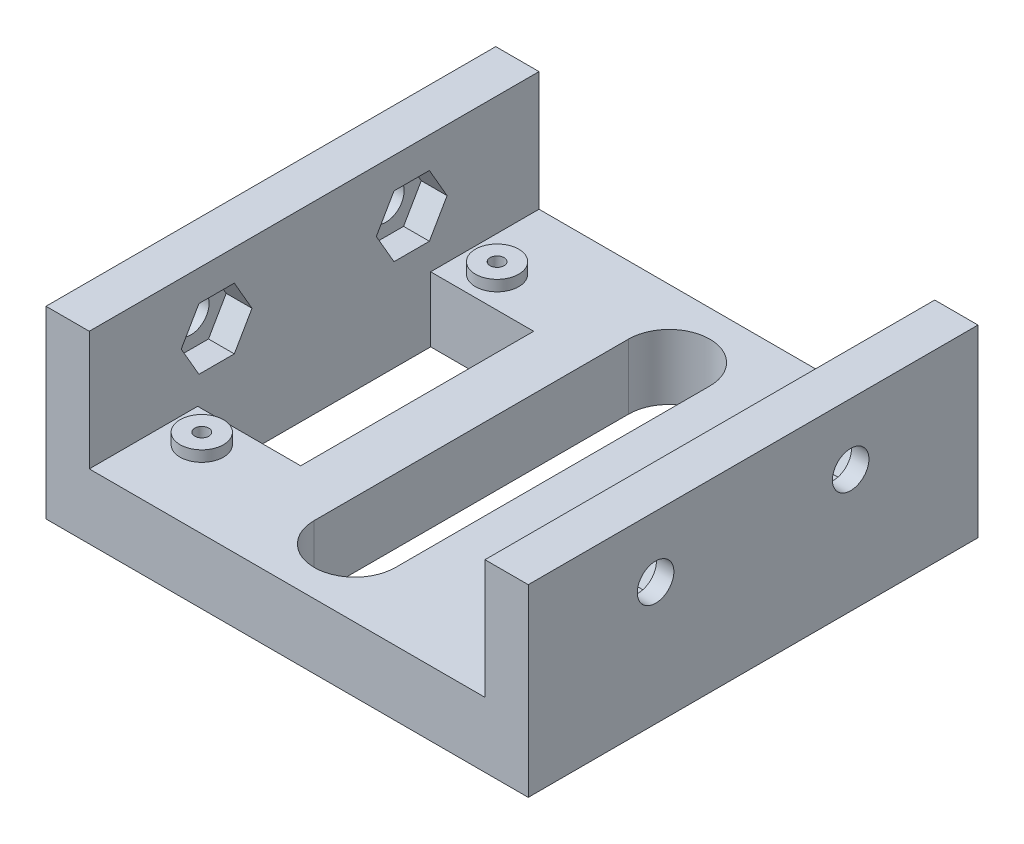
SolidWorks part; units mm, degrees
ref_plane "Front Plane" through (0, 0, 0) normal (0, 0, 1) x (1, 0, 0)
ref_plane "Top Plane" through (0, 0, 0) normal (0, 1, 0) x (1, 0, 0)
ref_plane "Right Plane" through (0, 0, 0) normal (1, 0, 0) x (0, 0, -1)
sketch "Sketch1" plane through (0, 0, 0) normal (0, 1, 0) x (1, 0, 0)
  line L9 (-44.5, 0) -> (44.5, 0)
  line L10 (-44.5, 0) -> (-44.5, 83)
  line L11 (-44.5, 83) -> (44.5, 83)
  line L12 (44.5, 0) -> (44.5, 83)
  line L13 (34.5, 0) -> (-34.5, 0) construction
  line L14 (34.5, 0) -> (34.5, 83) construction
  line L15 (34.5, 83) -> (-34.5, 83) construction
  line L16 (-34.5, 0) -> (-34.5, 83) construction
  line L21 (-30, 14.25) -> (30, 14.25) construction
  line L22 (-30, 14.25) -> (-30, 68.75) construction
  line L23 (-30, 68.75) -> (30, 68.75) construction
  line L24 (30, 14.25) -> (30, 68.75) construction
  line L27 (-7.5, 70.5) -> (-7.5, 12.5)
  line L29 (7.5, 12.5) -> (7.5, 70.5)
  circle A0 centre (30, 14.25) radius 1.3
  circle A1 centre (-30, 14.25) radius 1.3
  circle A2 centre (-30, 68.75) radius 1.3
  circle A3 centre (30, 68.75) radius 1.3
  circle A4 centre (-30, 68.75) radius 1.75 construction
  circle A6 centre (0, 70.5) radius 7.5
  circle A7 centre (0, 12.5) radius 7.5
  point P9 (0, 0)
  point P10 (0, 0)
  point P25 (0, 14.25)
  point P27 (44.5, 41.5)
  point P28 (30, 41.5)
  dimension "D7" = 2.6
  dimension "D8" = 3.5
  dimension "D1" = 83
  dimension "D2" = 69
  dimension "D3" = 10
  dimension "D4" = 15
  dimension "D5" = 5
  dimension "D6" = 5
  dimension "D9" = 60
  dimension "D10" = 54.5
extrude "Main Body" add sketch "Sketch1" along normal blind 14 contours L9 L12 L11 L10 A3 A2 A1 A0 region at (-43.283, 0, -41.5)
sketch "Sketch2" plane through (0, 14, 0) normal (0, 1, 0) x (1, 0, 0)
  line L1 (-36.5125, 0) -> (36.5125, 0)
  line L2 (-36.5125, 0) -> (-36.5125, 83)
  line L3 (-36.5125, 83) -> (36.5125, 83)
  line L4 (36.5125, 0) -> (36.5125, 83)
  line L7 (-44.5, 83) -> (44.5, 83) construction
  circle A2 centre (-30, 14.25) radius 4
  circle A3 centre (30, 14.25) radius 4
  circle A4 centre (-30, 68.75) radius 4
  circle A5 centre (30, 68.75) radius 4
  point P8 (0, 0)
  dimension "D2" = 8
  dimension "D1" = 73.025
extrude "Screw Riser" cut sketch "Sketch2" against normal blind 2
sketch "Sketch4" plane through (0, 14, 0) normal (0, 1, 0) x (1, 0, 0)
  line L0 (-44.5, 0) -> (-36.5125, 0) construction
  line L1 (-44.5, 83) -> (-36.5125, 83)
  line L2 (-44.5, 83) -> (-44.5, 0)
  line L3 (-44.5, 0) -> (-36.5125, 0)
  line L4 (-36.5125, 83) -> (-36.5125, 0)
  line L5 (36.5125, 83) -> (44.5, 83) construction
  line L6 (44.5, 0) -> (36.5125, 0)
  line L7 (44.5, 0) -> (44.5, 83)
  line L8 (44.5, 83) -> (36.5125, 83)
  line L9 (36.5125, 0) -> (36.5125, 83)
extrude "Topper Support" add sketch "Sketch4" along normal offset from surface (20 mm away) 34 up to face at (0, 0, -41.5)
sketch "Sketch6" plane through (-44.5, 0, 0) normal (-1, 0, 0) x (0, 0, 1)
  line L0 (-52.9696, 22.6555) -> (-56.2348, 28.3109)
  line L1 (-53.0842, 22.6555) -> (-56.2921, 28.2117) construction
  line L2 (-56.2921, 28.2117) -> (-62.7079, 28.2117) construction
  line L3 (-62.7079, 28.2117) -> (-65.9158, 22.6555) construction
  line L4 (-65.9158, 22.6555) -> (-62.7079, 17.0992) construction
  line L5 (-62.7079, 17.0992) -> (-56.2921, 17.0992) construction
  line L6 (-56.2921, 17.0992) -> (-53.0842, 22.6555) construction
  line L7 (-56.2348, 28.3109) -> (-62.7652, 28.3109)
  line L8 (-62.7652, 28.3109) -> (-66.0304, 22.6555)
  line L9 (-66.0304, 22.6555) -> (-62.7652, 17)
  line L10 (-62.7652, 17) -> (-56.2348, 17)
  line L11 (-56.2348, 17) -> (-52.9696, 22.6555)
  line L12 (-23.5, 22.6555) -> (-59.5, 22.6555) construction
  line L13 (-16.9696, 22.6555) -> (-20.2348, 28.3109)
  line L14 (-20.2348, 28.3109) -> (-26.7652, 28.3109)
  line L15 (-26.7652, 28.3109) -> (-30.0304, 22.6555)
  line L16 (-30.0304, 22.6555) -> (-26.7652, 17)
  line L17 (-26.7652, 17) -> (-20.2348, 17)
  line L18 (-20.2348, 17) -> (-16.9696, 22.6555)
  line L19 (0, 0) -> (-83, 0) construction
  line L20 (-83, 34) -> (0, 34) construction
  circle A0 centre (-59.5, 22.6555) radius 5.5563 construction
  circle A1 centre (-23.5, 22.6555) radius 5.6555 construction
  point P26 (-41.5, 0)
  point P27 (-41.5, 22.6555)
  dimension "D1" = 11.1125
  dimension "D3" = 36
  dimension "D4" = 17
  dimension "D2" = 0.0992
extrude "Mount Nuts" cut sketch "Sketch6" along normal offset from surface (41.275 mm away) 4.7625 from surface up to face at (-36.5125, 23, -41.5) offset beyond the face yes starting at plane "Right Plane"
sketch "Sketch5" plane through (-36.5125, 0, 0) normal (-1, 0, 0) x (0, 0, 1)
  line L0 (0, 0) -> (-83, 0) construction
  line L1 (-20.2348, 17) -> (-26.7652, 28.3109) construction
  line L4 (-59.5, 22.6555) -> (-23.5, 22.6555) construction
  circle A0 centre (-59.5, 22.6555) radius 3.175 construction
  circle A1 centre (-23.5, 22.6555) radius 3.175 construction
  circle A2 centre (-59.5, 22.6555) radius 3.3734
  circle A3 centre (-23.5, 22.6555) radius 3.3734
  circle A4 centre (-23.5, 22.6555) radius 7.9375 construction
  circle A5 centre (-59.5, 22.6555) radius 7.9375 construction
  point P2 (-23.5, 22.6555)
  point P3 (-41.5, 0)
  point P4 (-41.5, 22.6555)
  dimension "D2" = 6.35
  dimension "D5" = 15.875
  dimension "D3" = 0.1984
extrude "9/32 Mount Holes" cut sketch "Sketch5" along normal up to next
sketch "Sketch8" plane through (0, 14, 0) normal (0, 1, 0) x (1, 0, 0)
  line L17 (-7.5, 12.5) -> (-7.5, 70.5) construction
  line L33 (-36.5125, 0) -> (36.5125, 0) construction
  line L34 (-36.5125, 20) -> (36.5125, 20) construction
  line L35 (-36.5125, 20) -> (-36.5125, 63) construction
  line L36 (-36.5125, 63) -> (36.5125, 63) construction
  line L37 (36.5125, 20) -> (36.5125, 63) construction
  line L38 (36.5125, 83) -> (-36.5125, 83) construction
  line L39 (36.5125, 83) -> (36.5125, 0) construction
  line L40 (-36.5125, 0) -> (-36.5125, 83) construction
  line L42 (-36.5125, 63) -> (-17.5, 63)
  line L43 (-36.5125, 63) -> (-36.5125, 20)
  line L44 (-36.5125, 20) -> (-17.5, 20)
  line L45 (-17.5, 63) -> (-17.5, 20)
  line L47 (36.5125, 63) -> (17.5, 63)
  line L48 (36.5125, 63) -> (36.5125, 20)
  line L49 (36.5125, 20) -> (17.5, 20)
  line L50 (17.5, 63) -> (17.5, 20)
  dimension "D1" = 20
  dimension "D2" = 20
  dimension "D3" = 10
extrude "Middle Cut" cut sketch "Sketch8" against normal up to surface (14 mm away) up to face at (0, 0, -41.5)
sketch "Sketch9" plane through (36.5125, 0, 0) normal (-1, 0, 0) x (0, 0, 1)
  line L0 (-26.7652, 17) -> (-30.0304, 22.6555) construction
  line L1 (-30.0304, 22.6555) -> (-26.7652, 28.3109) construction
  line L2 (-26.7652, 28.3109) -> (-20.2348, 28.3109) construction
  line L3 (-20.2348, 28.3109) -> (-16.9696, 22.6555) construction
  line L4 (-16.9696, 22.6555) -> (-20.2348, 17) construction
  line L5 (-20.2348, 17) -> (-26.7652, 17) construction
  line L6 (-62.7652, 17) -> (-66.0304, 22.6555) construction
  line L7 (-66.0304, 22.6555) -> (-62.7652, 28.3109) construction
  line L8 (-62.7652, 28.3109) -> (-56.2348, 28.3109) construction
  line L9 (-56.2348, 28.3109) -> (-52.9696, 22.6555) construction
  line L10 (-52.9696, 22.6555) -> (-56.2348, 17) construction
  line L11 (-56.2348, 17) -> (-62.7652, 17) construction
  line L12 (-26.7652, 17) -> (-30.0304, 22.6555)
  line L13 (-30.0304, 22.6555) -> (-26.7652, 28.3109)
  line L14 (-26.7652, 28.3109) -> (-20.2348, 28.3109)
  line L15 (-20.2348, 28.3109) -> (-16.9696, 22.6555)
  line L16 (-16.9696, 22.6555) -> (-20.2348, 17)
  line L17 (-20.2348, 17) -> (-26.7652, 17)
  line L18 (-62.7652, 17) -> (-66.0304, 22.6555)
  line L19 (-66.0304, 22.6555) -> (-62.7652, 28.3109)
  line L20 (-62.7652, 28.3109) -> (-56.2348, 28.3109)
  line L21 (-56.2348, 28.3109) -> (-52.9696, 22.6555)
  line L22 (-52.9696, 22.6555) -> (-56.2348, 17)
  line L23 (-56.2348, 17) -> (-62.7652, 17)
  circle A0 centre (-59.5, 22.6555) radius 3.3734 construction
  circle A1 centre (-23.5, 22.6555) radius 3.3734 construction
  circle A2 centre (-59.5, 22.6555) radius 3.3734
  circle A3 centre (-23.5, 22.6555) radius 3.3734
extrude "Mount Nuts p2" cut sketch "Sketch9" against normal blind 4.7625 contours L23 L22 L21 L20 L19 L18 A2 | A2 | L17 L16 L15 L14 L13 L12 A3 | A3 | L18 L19 L20 L21 L22 L23 region at (36.5125, 19.9141, -28.2481) region at (36.5125, 19.9141, -64.2481) region at (36.5125, 22.6555, -59.5) region at (36.5125, 22.6555, -23.5)
extrude "9/32 Mount Holes p2" cut sketch "Sketch9<3>" against normal up to surface (7.9875 mm away) contours A2 | A3 region at (36.5125, 22.6555, -59.5) region at (36.5125, 22.6555, -23.5) up to face at (44.5, 17, -41.5)
sketch "Sketch9<3>" plane through (36.5125, 0, 0) normal (-1, 0, 0) x (0, 0, 1) same geometry as "Sketch9"
